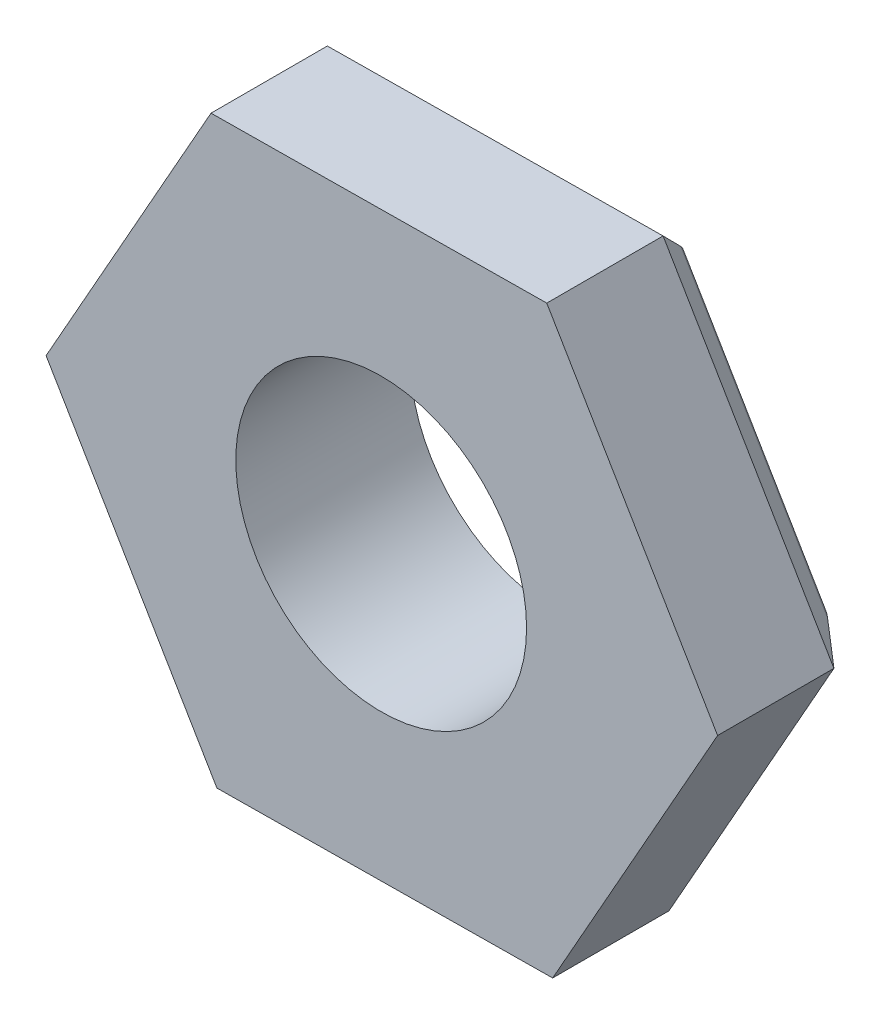
SolidWorks part; units mm, degrees
ref_plane "Alzado" through (0, 0, 0) normal (0, 0, 1) x (1, 0, 0)
ref_plane "Planta" through (0, 0, 0) normal (0, 1, 0) x (1, 0, 0)
ref_plane "Vista lateral" through (0, 0, 0) normal (1, 0, 0) x (0, 0, -1)
sketch "Croquis1" plane through (0, 0, 0) normal (0, 0, 1) x (1, 0, 0)
  line L1 (-52.4559, 17.977) -> (-49.6198, 23.006)
  line L2 (-49.6198, 23.006) -> (-52.557, 27.9765)
  line L3 (-52.557, 27.9765) -> (-58.3302, 27.9182)
  line L4 (-58.3302, 27.9182) -> (-61.1662, 22.8892)
  line L5 (-61.1662, 22.8892) -> (-58.2291, 17.9187)
  line L6 (-58.2291, 17.9187) -> (-52.4559, 17.977)
  circle A0 centre (-55.393, 22.9476) radius 5 construction
extrude "Saliente-Extruir1" add sketch "Croquis1" along normal blind 3
sketch "Croquis2" plane through (0, 0, 0) normal (0, 0, 1) x (1, 0, 0)
  circle A0 centre (-55.4042, 22.9665) radius 2.5
chamfer "Chaflán1" distance 1 angle 45 6 edges at (-51.0884, 25.4912, 0) (-55.4436, 27.9473, 0) (-59.7482, 25.4037, 0) (-59.6977, 20.4039, 0) (-55.3425, 17.9478, 0) (-51.0379, 20.4915, 0)
fillet "Redondeo1" radius 1 1 edges at (-58.8367, 20.9127, 0)
extrude "Cortar-Extruir1" cut sketch "Croquis2" along normal blind 5
fillet "Redondeo2" radius 1 9 edges at (-60.758, 22.8934, 0.6464) (-60.0384, 23.0083, 0.0761) (-58.0286, 18.2743, 0.6464) (-57.5808, 18.8491, 0.0761) (-58.7597, 25.1208, 0) (-55.4335, 26.9474, 0) (-51.9493, 24.9825, 0) (-51.9089, 20.9827, 0) (-55.1135, 18.9502, 0)
